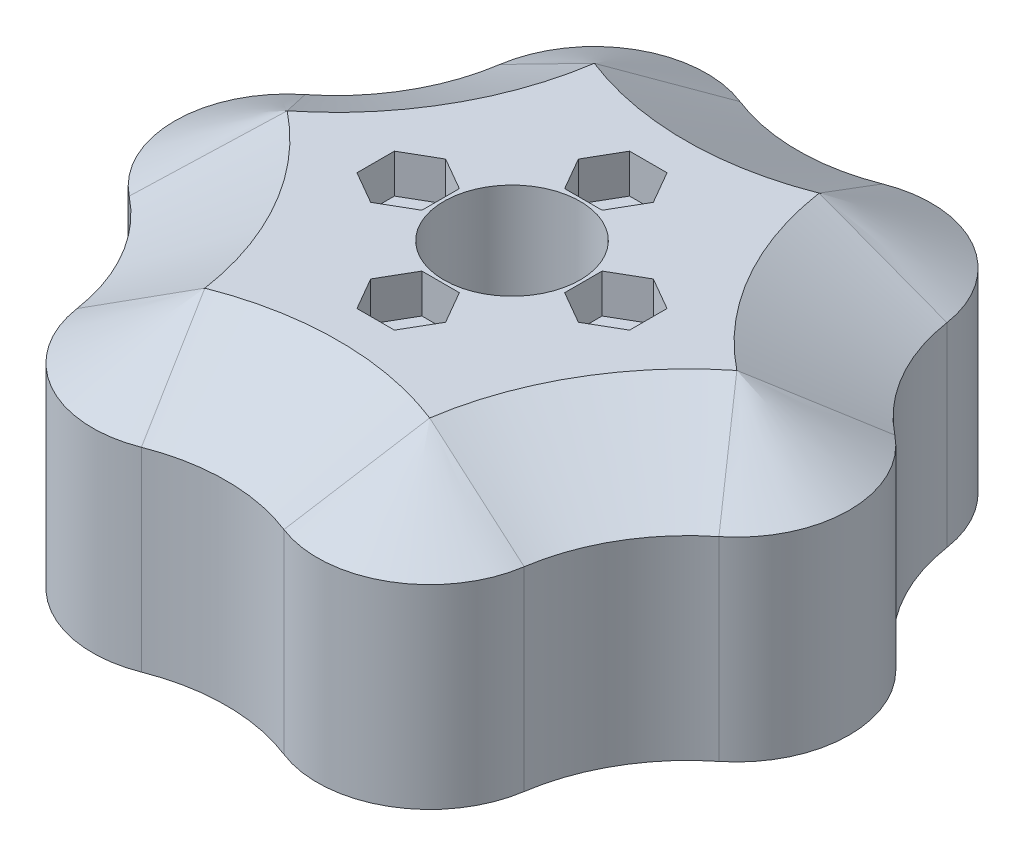
SolidWorks part; units mm, degrees
ref_plane "Front Plane" through (0, 0, 0) normal (0, 0, 1) x (1, 0, 0)
ref_plane "Top Plane" through (0, 0, 0) normal (0, 1, 0) x (1, 0, 0)
ref_plane "Right Plane" through (0, 0, 0) normal (1, 0, 0) x (0, 0, -1)
sketch "Sketch1" plane through (0, 0, 0) normal (0, 1, 0) x (1, 0, 0)
  line L0 (-8, 0) -> (8, 0) construction
  line L1 (-8.6603, 15) -> (-17.3205, 0)
  line L2 (-17.3205, 0) -> (-8.6603, -15)
  line L3 (-8.6603, -15) -> (8.6603, -15)
  line L4 (8.6603, -15) -> (17.3205, 0)
  line L5 (17.3205, 0) -> (8.6603, 15)
  line L6 (8.6603, 15) -> (-8.6603, 15)
  line L7 (0, 8) -> (0, -8) construction
  line L9 (-10.5, 1.4434) -> (-10.5, -1.4434)
  line L10 (-10.5, -1.4434) -> (-8, -2.8868)
  line L11 (-8, -2.8868) -> (-5.5, -1.4434)
  line L12 (-5.5, -1.4434) -> (-5.5, 1.4434)
  line L13 (-5.5, 1.4434) -> (-8, 2.8868)
  line L14 (-8, 2.8868) -> (-10.5, 1.4434)
  line L15 (1.4434, 10.5) -> (-1.4434, 10.5)
  line L16 (-1.4434, 10.5) -> (-2.8868, 8)
  line L17 (-2.8868, 8) -> (-1.4434, 5.5)
  line L18 (-1.4434, 5.5) -> (1.4434, 5.5)
  line L19 (1.4434, 5.5) -> (2.8868, 8)
  line L20 (2.8868, 8) -> (1.4434, 10.5)
  line L21 (5.5, 1.4434) -> (5.5, -1.4434)
  line L22 (5.5, -1.4434) -> (8, -2.8868)
  line L23 (8, -2.8868) -> (10.5, -1.4434)
  line L24 (10.5, -1.4434) -> (10.5, 1.4434)
  line L25 (10.5, 1.4434) -> (8, 2.8868)
  line L26 (8, 2.8868) -> (5.5, 1.4434)
  line L27 (-1.4434, -5.5) -> (-2.8868, -8)
  line L28 (-2.8868, -8) -> (-1.4434, -10.5)
  line L29 (-1.4434, -10.5) -> (1.4434, -10.5)
  line L30 (1.4434, -10.5) -> (2.8868, -8)
  line L31 (2.8868, -8) -> (1.4434, -5.5)
  line L32 (1.4434, -5.5) -> (-1.4434, -5.5)
  circle A0 centre (0, 0) radius 15 construction
  arc A1 (0, 15) -> (-12.9904, 7.5) centre (-8.6603, 15) ccw
  arc A2 (12.9904, 7.5) -> (0, 15) centre (8.6603, 15) ccw
  arc A3 (12.9904, -7.5) -> (12.9904, 7.5) centre (17.3205, 0) ccw
  arc A4 (0, -15) -> (12.9904, -7.5) centre (8.6603, -15) ccw
  arc A5 (-12.9904, -7.5) -> (0, -15) centre (-8.6603, -15) ccw
  arc A6 (-8.9775, -2.3224) -> (-8.9722, -2.3032) centre (-17.3205, 0) ccw
  circle A7 centre (0, 0) radius 5.25
  circle A8 centre (0, 8) radius 1.5
  circle A9 centre (0, -8) radius 1.5
  circle A10 centre (8, 0) radius 1.5
  circle A11 centre (-8, 0) radius 1.5
  circle A12 centre (-8, 0) radius 2.5 construction
  circle A13 centre (0, 8) radius 2.5 construction
  circle A14 centre (8, 0) radius 2.5 construction
  arc A15 (2.1238, -9.319) -> (-2.1238, -9.319) centre (0, -8) ccw construction
  arc A16 (-2.1238, -9.319) -> (-2.1282, -9.3139) centre (-8.6603, -15) ccw
  arc A17 (2.1282, -9.3139) -> (2.1238, -9.319) centre (8.6603, -15) ccw
  arc A18 (8.9775, 2.3224) -> (8.9722, 2.3032) centre (17.3205, 0) ccw
  arc A19 (2.1238, 9.319) -> (2.1282, 9.3139) centre (8.6603, 15) ccw
  arc A20 (-2.1282, 9.3139) -> (-2.1238, 9.319) centre (-8.6603, 15) ccw
  arc A21 (-12.9904, 7.5) -> (-12.9904, -7.5) centre (-17.3205, 0) ccw
  arc A22 (-8.9722, 2.3032) -> (-8.9775, 2.3224) centre (-17.3205, 0) ccw
  arc A23 (8.9722, -2.3032) -> (8.9775, -2.3224) centre (17.3205, 0) ccw
  point P11 (0, 15)
  point P26 (0, 0)
  point P27 (0, 0)
  dimension "D1" = 10.5
  dimension "D3" = 3
  dimension "D2" = 16
  dimension "D4" = 5
  dimension "D5" = 30
extrude "Boss-Extrude1" add sketch "Sketch1" along normal blind 20 contours L1 A21 L2 | L5 L6 L1 L2 L3 L4 A7 L32 L31 L30 L29 L28 L27 L26 L25 L24 L23 L22 L21 L20 L19 L18 L17 L16 L15 L14 L13 L12 L11 L10 L9 | L6 A1 L1 | L5 A2 L6 | L4 A3 L5 | L3 A4 L4 | L2 A5 L3 region at (-4.3301, 0, -14.5417) region at (-9.8539, 0, -17.0675) region at (-19.7078, 0, 0) region at (9.8539, 0, -17.0675) region at (-9.8539, 0, 17.0675) region at (19.7078, 0, 0) region at (9.8539, 0, 17.0675)
extrude "Boss-Extrude2" add sketch "Sketch1<3>" along normal offset from surface (17 mm away) 3 contours L13 L14 L9 L10 L11 L12 A11 | L19 L20 L15 L16 L17 L18 A8 | L25 L26 L21 L22 L23 L24 A10 | L31 L32 L27 L28 L29 L30 A9 region at (-9.7005, 0, -1.8168) region at (1.7196, 0, -9.8687) region at (6.7882, 0, -2.0989) region at (0, 0, 5.5764) up to face at (0, 20, 0)
sketch "Sketch1<3>" plane through (0, 0, 0) normal (0, 1, 0) x (1, 0, 0) same geometry as "Sketch1"
fillet "Fillet1" radius 15 6 edges at (0, 10, 15) (12.9904, 10, 7.5) (12.9904, 10, -7.5) (0, 10, -15) (-12.9904, 10, -7.5) (-12.9904, 10, 7.5)
chamfer "Chamfer1" distance 5 angle 60 12 edges at (0, 20, 22.0183) (12.9904, 20, 22.5) (-12.9904, 20, 22.5) (19.0684, 20, 11.0092) (-19.0684, 20, 11.0092) (25.9808, 20, 0) (-25.9808, 20, 0) (19.0684, 20, -11.0092) (-19.0684, 20, -11.0092) (12.9904, 20, -22.5) (-12.9904, 20, -22.5) (0, 20, -22.0183) first distance on face at (0, 10, 22.5388) first distance on face at (12.174, 10, 21.0859) first distance on face at (-12.174, 10, 21.0859) first distance on face at (19.5192, 10, 11.2694) first distance on face at (-19.5192, 10, 11.2694) first distance on face at (24.3479, 10, 0) first distance on face at (-24.3479, 10, 0) first distance on face at (19.5192, 10, -11.2694) first distance on face at (-19.5192, 10, -11.2694) first distance on face at (12.174, 10, -21.0859) first distance on face at (-12.174, 10, -21.0859) first distance on face at (0, 10, -22.5388)
